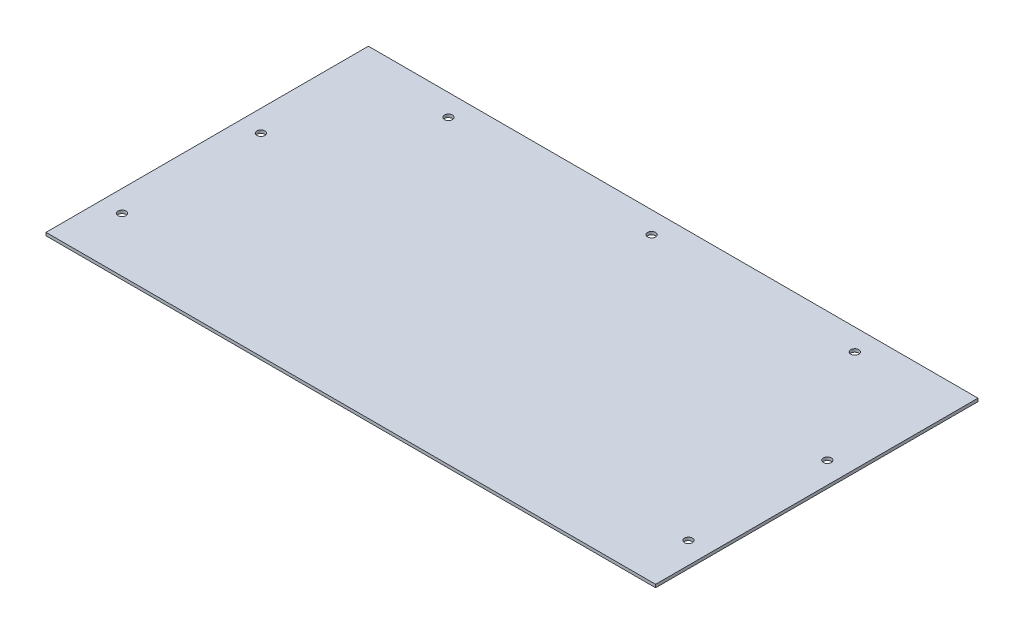
SolidWorks part; units mm, degrees
material "6061-T6 (SS)"
ref_plane "X-Y Datum" through (0, 0, 0) normal (0, 0, 1) x (1, 0, 0)
ref_plane "X-Z Datum" through (0, 0, 0) normal (0, 1, 0) x (1, 0, 0)
ref_plane "Y-Z Datum" through (0, 0, 0) normal (1, 0, 0) x (0, 0, -1)
sketch "Sketch1" plane through (0, 0, 0) normal (0, 0, 1) x (1, 0, 0)
  line L1 (-228.6, -1.143) -> (228.6, -1.143)
  line L2 (-228.6, -1.143) -> (-228.6, 1.143)
  line L3 (-228.6, 1.143) -> (228.6, 1.143)
  line L4 (228.6, -1.143) -> (228.6, 1.143)
  line L5 (-228.6, -1.143) -> (228.6, 1.143) construction
  line L6 (-228.6, 1.143) -> (228.6, -1.143) construction
  point P0 (0, 0)
  dimension "D1" = 2.286
  dimension "D2" = 457.2
extrude "Boss-Extrude1" add sketch "Sketch1" along normal blind 238.62
sketch "Sketch2" plane through (0, 0, 0) normal (0, 0, -1) x (-1, 0, 0)
  line L22 (-228.6, 1.143) -> (-228.6, -1.143)
  line L23 (-228.6, -1.143) -> (228.6, -1.143)
  line L24 (228.6, -1.143) -> (228.6, 1.143)
  line L25 (228.6, 1.143) -> (-228.6, 1.143)
  line L26 (-228.6, 1.143) -> (-228.6, -1.143)
  line L27 (-228.6, -1.143) -> (228.6, -1.143)
  line L28 (228.6, -1.143) -> (228.6, 1.143)
  line L29 (228.6, 1.143) -> (-228.6, 1.143)
  line M6 (-228.6, -1.143) -> (228.6, -1.143)
  line M8 (228.6, 1.143) -> (-228.6, 1.143)
  dimension "D1" = 0
extrude "Boss-Extrude2" add sketch "Sketch2" along normal blind 3.175 contours M8 M6 | M8 M6 region at (0, 0, 0)
sketch "Sketch6" plane through (0, -1.143, 0) normal (0, -1, 0) x (1, 0, 0)
  circle A0 centre (-212.419, 197.7848) radius 3 construction
  circle A1 centre (212.419, 197.7848) radius 3 construction
  circle A2 centre (212.419, 93.6448) radius 3 construction
  circle A3 centre (152.4, 13.0175) radius 3 construction
  circle A4 centre (0, 13.0175) radius 3 construction
  circle A5 centre (-152.4, 13.0175) radius 3 construction
  circle A6 centre (-212.419, 93.6448) radius 3 construction
  circle A7 centre (-212.419, 197.7848) radius 3
  circle A8 centre (212.419, 197.7848) radius 3
  circle A9 centre (212.419, 93.6448) radius 3
  circle A10 centre (152.4, 13.0175) radius 3
  circle A11 centre (0, 13.0175) radius 3
  circle A12 centre (-152.4, 13.0175) radius 3
  circle A13 centre (-212.419, 93.6448) radius 3
extrude "Cut-Extrude6" cut sketch "Sketch6" against normal blind 2.286
